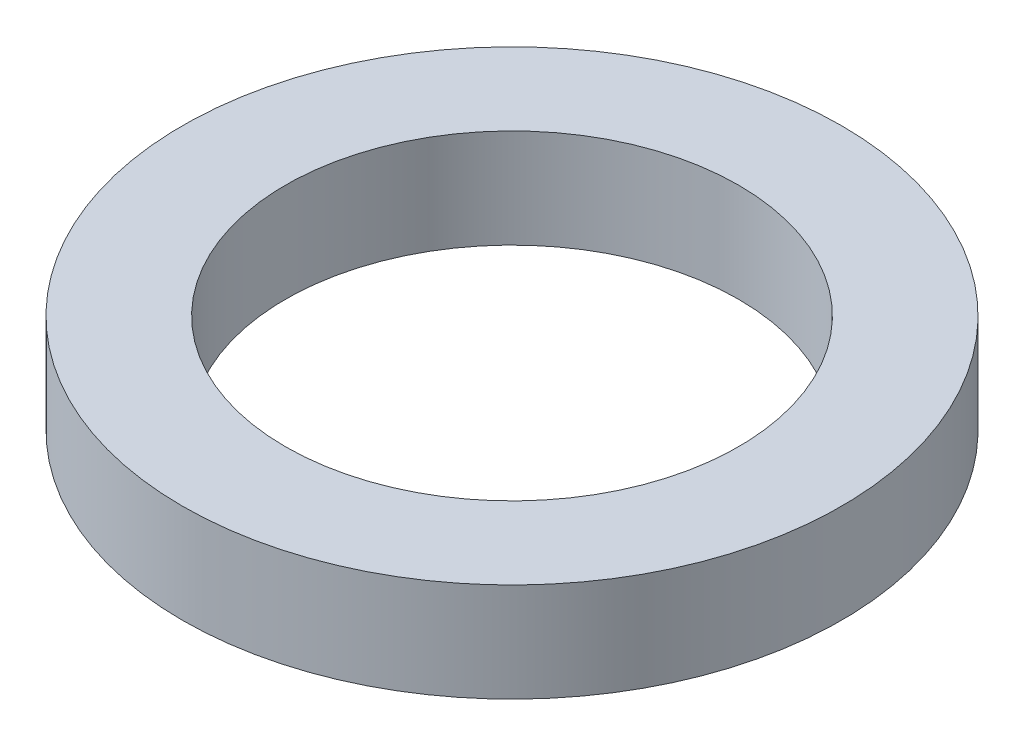
SolidWorks part; units mm, degrees
ref_plane "Front Plane" through (0, 0, 0) normal (0, 0, 1) x (1, 0, 0)
ref_plane "Top Plane" through (0, 0, 0) normal (0, 1, 0) x (1, 0, 0)
ref_plane "Right Plane" through (0, 0, 0) normal (1, 0, 0) x (0, 0, -1)
sketch "Sketch1" plane through (0, 0, 0) normal (0, 1, 0) x (1, 0, 0)
  circle A0 centre (0, 0) radius 40
  dimension "FLANGE_OD" = 80
extrude "Boss-Extrude1" add sketch "Sketch1" along normal blind 12
sketch "Sketch2" plane through (0, 0, 0) normal (0, 1, 0) x (1, 0, 0)
  circle A0 centre (0, 0) radius 27.5
  dimension "BORE_D" = 55
extrude "Cut-Extrude1" cut sketch "Sketch2" along normal through all
sketch "Sketch3" plane through (0, 12, 0) normal (0, 1, 0) x (1, 0, 0)
  circle A0 centre (0, 0) radius 16.2726 construction
  circle A1 centre (-16.2726, 0) radius 2.22
  dimension "BOLT_D" = 4.44
  dimension "BOLT_PCD" = 32.5451
extrude "Cut-Extrude2" cut sketch "Sketch3" against normal blind 9.9436 rebuild error yes
pattern_circular "CirPattern1" count 6 over 360 rebuild error yes
